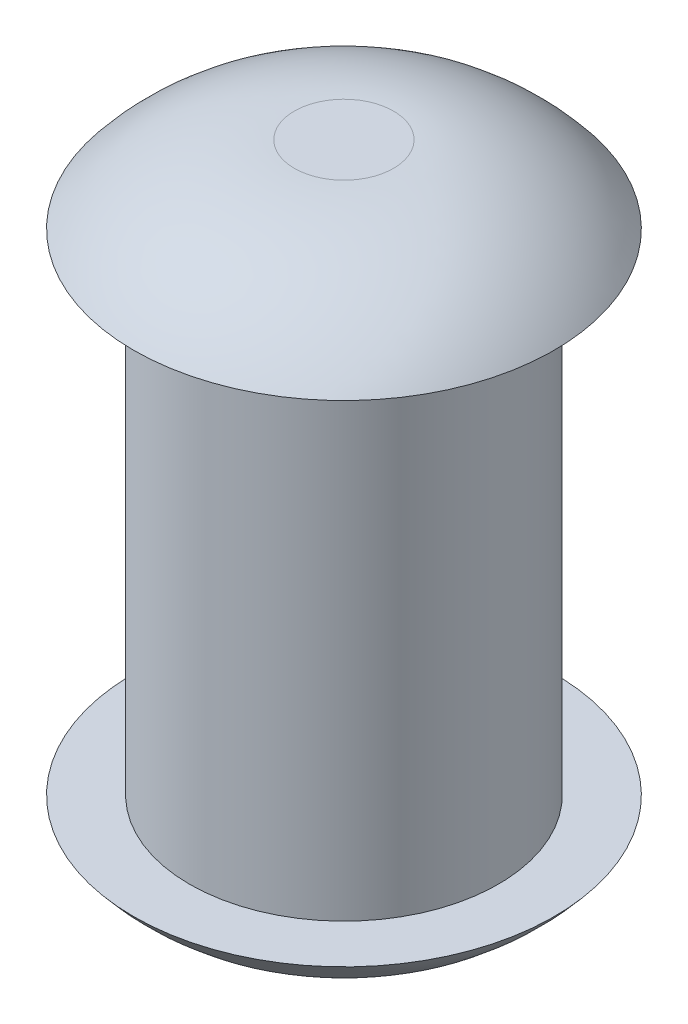
SolidWorks part; units mm, degrees
ref_plane "Płaszczyzna przednia" through (0, 0, 0) normal (0, 0, 1) x (1, 0, 0)
ref_plane "Płaszczyzna górna" through (0, 0, 0) normal (0, 1, 0) x (1, 0, 0)
ref_plane "Płaszczyzna prawa" through (0, 0, 0) normal (1, 0, 0) x (0, 0, -1)
sketch "Szkic1" plane through (0, 0, 0) normal (0, 1, 0) x (1, 0, 0)
  circle A0 centre (0, 0) radius 3
  dimension "D1" = 6
extrude "Dodanie-wyciągnięcie1" add sketch "Szkic1" along normal blind 9.53
sketch "Szkic2" plane through (0, 9.53, 0) normal (0, 1, 0) x (1, 0, 0)
  circle A0 centre (0, 0) radius 4.0868
extrude "Dodanie-wyciągnięcie2" add sketch "Szkic2" along normal blind 1.5
fillet "Zaokrąglenie1" radius 4 1 edges at (0, 11.03, 4.0868)
ref_plane "Płaszczyzna1" through (0, 4.765, 0) normal (0, -1, 0) x (-1, 0, 0)
mirror "Lustro1" about plane through (0, 4.765, 0) normal (0, -1, 0) of bodies 102
